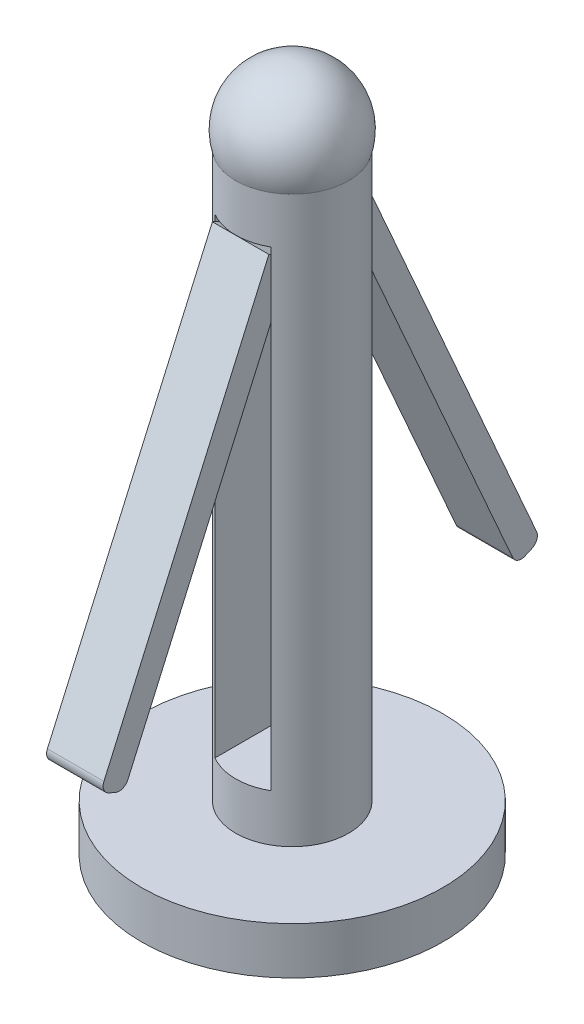
SolidWorks part; units mm, degrees
ref_plane "Front Plane" through (0, 0, 0) normal (0, 0, 1) x (1, 0, 0)
ref_plane "Top Plane" through (0, 0, 0) normal (0, 1, 0) x (1, 0, 0)
ref_plane "Right Plane" through (0, 0, 0) normal (1, 0, 0) x (0, 0, -1)
sketch "Sketch1" plane through (0, 0, 0) normal (0, 1, 0) x (1, 0, 0)
  circle A0 centre (0, 0) radius 16
extrude "Boss-Extrude1" add sketch "Sketch1" against normal blind 5
sketch "Sketch2" plane through (0, 0, 0) normal (0, 1, 0) x (1, 0, 0)
  circle A0 centre (0, 0) radius 6
extrude "Boss-Extrude2" add sketch "Sketch2" along normal blind 60
dome "Dome1" faces to dome 1 distance 8 reverse direction no elliptical dome no face at (0, 60, 6) parameters "D1"=8
sketch "Sketch3" plane through (0, 0, 0) normal (0, 0, 1) x (1, 0, 0)
  line L1 (2.9762, 55) -> (-3.0238, 55)
  line L2 (2.9762, 55) -> (2.9762, 5)
  line L3 (2.9762, 5) -> (-3.0238, 5)
  line L4 (-3.0238, 55) -> (-3.0238, 5)
  line L5 (2.9762, 55) -> (-3.0238, 5) construction
  line L6 (2.9762, 5) -> (-3.0238, 55) construction
  point P0 (-0.0238, 30)
  dimension "D1" = 6
  dimension "D2" = 50
  dimension "D3" = 30
extrude "Cut-Extrude1" cut sketch "Sketch3" along normal blind 6 and the other way blind 6
sketch "Sketch4" plane through (2.9762, 0, 0) normal (-1, 0, 0) x (0, 0, 1)
  line L0 (5.4546, 54.4451) -> (23.3751, 13.8294)
  line L1 (23.3751, 13.8294) -> (20.835, 12.7086)
  line L2 (20.835, 12.7086) -> (2.9145, 53.3243)
  line L3 (5.4546, 54.4451) -> (2.9145, 53.3243)
extrude "Boss-Extrude6" add sketch "Sketch4" along normal blind 6
fillet "Fillet2" radius 1 1 edges at (-0.0238, 13.8294, 23.3751) type face fillet first side face at (-0.0238, 34.1372, 14.4149) second side face at (-0.0238, 13.269, 22.1051)
fillet "Fillet4" radius 1 1 edges at (-0.0238, 12.7086, 20.835) type face fillet first side face at (-0.0238, 38.062, 9.6485) second side face at (-0.0238, 13.0672, 21.6476)
mirror "Mirror2" about plane through (0, 0, 0) normal (0, 0, 1) of "Fillet2", "Fillet4", "Boss-Extrude6"
ref_point "Point1"
ref_point "Point2"
ref_axis "Axis1" through (0, 0, 0) along (0, -1, 0)
